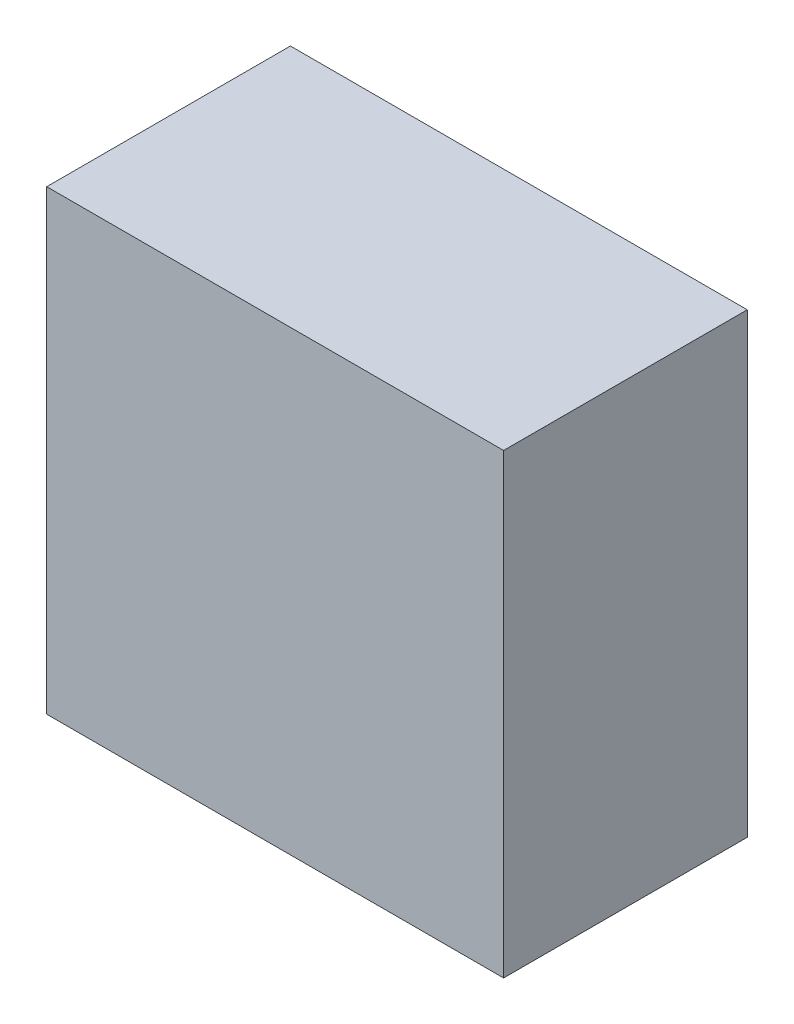
SolidWorks part; units mm, degrees
material "Custom Plastic"
ref_plane "Front Plane" through (0, 0, 0) normal (0, 0, 1) x (1, 0, 0)
ref_plane "Top Plane" through (0, 0, 0) normal (0, 1, 0) x (1, 0, 0)
ref_plane "Right Plane" through (0, 0, 0) normal (1, 0, 0) x (0, 0, -1)
other "Configuration Table"
sketch "Sketch1" plane through (0, 0, 0) normal (0, 0, 1) x (1, 0, 0)
  circle A0 centre (0, 0) radius 10
  dimension "D1" = 20
extrude "Boss-Extrude1" add sketch "Sketch1" along normal mid plane 10
sketch "Sketch2" plane through (0, 0, 0) normal (0, 0, 1) x (1, 0, 0)
  line L1 (-15, -15) -> (15, -15)
  line L2 (-15, -15) -> (-15, 15)
  line L3 (-15, 15) -> (15, 15)
  line L4 (15, -15) -> (15, 15)
  line L5 (-15, -15) -> (15, 15) construction
  line L6 (-15, 15) -> (15, -15) construction
  circle A0 centre (0, 0) radius 12
  dimension "D1" = 24
  dimension "D2" = 30
extrude "Boss-Extrude2" add sketch "Sketch2" along normal mid plane 12 separate body
sketch "Sketch3" plane through (0, 0, 6) normal (0, 0, 1) x (1, 0, 0)
  line L4 (15, -15) -> (15, 15)
  line L5 (15, 15) -> (-15, 15)
  line L6 (-15, 15) -> (-15, -15)
  line L7 (-15, -15) -> (15, -15)
  line L8 (15, -15) -> (15, 15)
  line L9 (15, 15) -> (-15, 15)
  line L10 (-15, 15) -> (-15, -15)
  line L11 (-15, -15) -> (15, -15)
  dimension "D1" = 0
extrude "Boss-Extrude3" add sketch "Sketch3" along normal blind 2
mirror "Mirror1" about plane through (0, 0, 0) normal (0, 0, 1) of "Boss-Extrude3"
